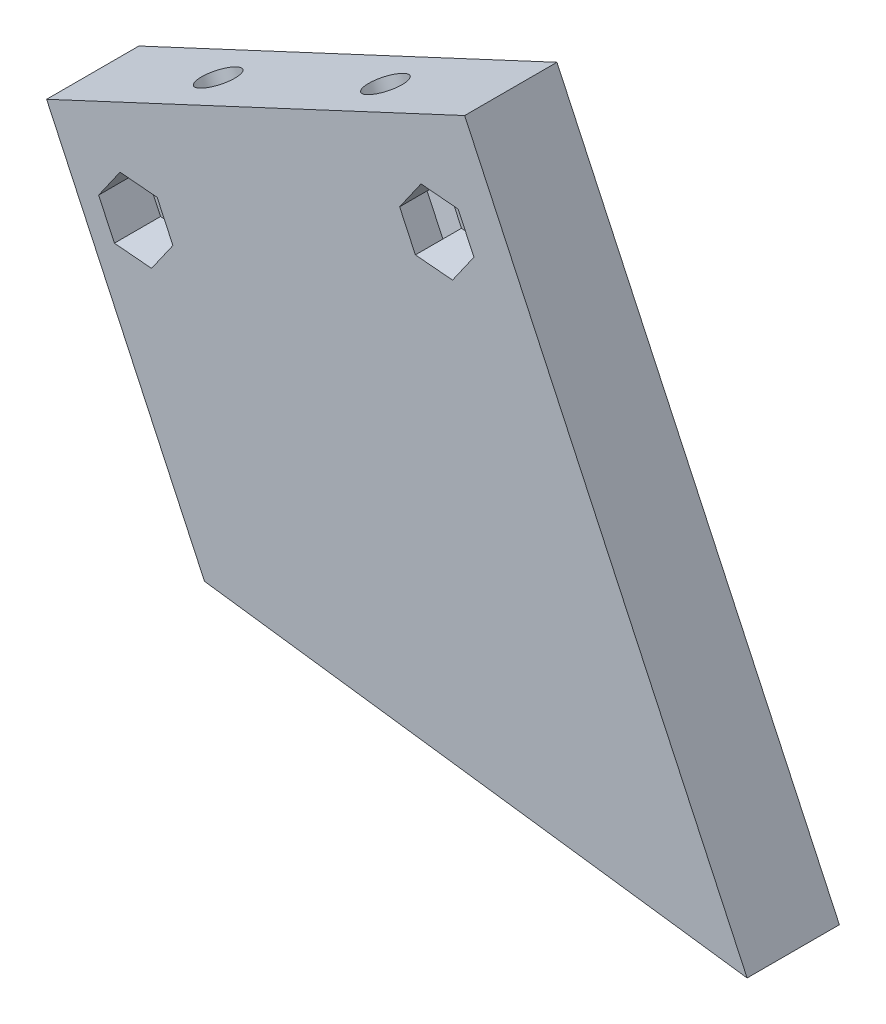
SolidWorks part; units mm, degrees
material "ABS"
ref_plane "Front Plane" through (0, 0, 0) normal (0, 0, 1) x (1, 0, 0)
ref_plane "Top Plane" through (0, 0, 0) normal (0, 1, 0) x (1, 0, 0)
ref_plane "Right Plane" through (0, 0, 0) normal (1, 0, 0) x (0, 0, -1)
sketch "Sketch1" plane through (0, 0, 0) normal (0, 0, 1) x (1, 0, 0)
  line L0 (117.7638, -15.9332) -> (87.1479, 49.7228)
  line L1 (273.6131, -36.6769) -> (75.3615, -10.2894) construction
  line L2 (87.1479, 49.7228) -> (41.8325, 28.5919)
  line L3 (41.8325, 28.5919) -> (58.9442, -8.1043)
  line L4 (58.9442, -8.1043) -> (117.7638, -15.9332)
  line L5 (117.7638, -15.9332) -> (87.1479, 49.7228) construction
  line L6 (189.2372, 97.3278) -> (-129.7831, -51.4338) construction
  dimension "D1" = 50
extrude "Boss-Extrude1" add sketch "Sketch1" against normal blind 10
sketch "Sketch2" plane through (-3.4798, 7.4624, 0) normal (-0.4226, 0.9063, 0) x (0.9063, 0.4226, 0)
  line L0 (49.9966, 5) -> (99.9966, 5) construction
  line L1 (49.9966, 10) -> (49.9966, 0) construction
  line L2 (99.9966, 10) -> (99.9966, 0) construction
  line L3 (74.9966, 10) -> (74.9966, 0) construction
  line L4 (84.9966, 0.9585) -> (88.4966, 2.9793)
  line L5 (88.4966, 2.9793) -> (88.4966, 7.0207)
  line L6 (88.4966, 7.0207) -> (84.9966, 9.0415)
  line L7 (84.9966, 9.0415) -> (81.4966, 7.0207)
  line L8 (81.4966, 7.0207) -> (81.4966, 2.9793)
  line L9 (81.4966, 2.9793) -> (84.9966, 0.9585)
  line L10 (99.9966, 10) -> (49.9966, 10) construction
  line L11 (99.9966, 0) -> (49.9966, 0) construction
  line L12 (68.4966, 2.9793) -> (64.9966, 0.9585)
  line L13 (64.9966, 0.9585) -> (61.4966, 2.9793)
  line L14 (68.4966, 7.0207) -> (68.4966, 2.9793)
  line L15 (64.9966, 9.0415) -> (68.4966, 7.0207)
  line L16 (61.4966, 7.0207) -> (64.9966, 9.0415)
  line L17 (61.4966, 2.9793) -> (61.4966, 7.0207)
  circle A0 centre (84.9966, 5) radius 3.5 construction
  circle A1 centre (84.9966, 5) radius 2
  circle A2 centre (64.9966, 5) radius 3.5 construction
  circle A3 centre (64.9966, 5) radius 2
  dimension "D3" = 4
  dimension "D1" = 15
  dimension "D2" = 7
extrude "Cut-Extrude1" cut sketch "Sketch2" against normal through all contours A3 | A1 region at (73.5533, 43.3835, -5) region at (55.4272, 34.9312, -5)
extrude "Cut-Extrude2" cut sketch "Sketch2<3>" against normal through all from offset 4 offset against normal yes
sketch "Sketch2<3>" plane through (-3.4798, 7.4624, 0) normal (-0.4226, 0.9063, 0) x (0.9063, 0.4226, 0) same geometry as "Sketch2"
sketch "Sketch3" plane through (-0.0338, -0.2542, 0) normal (-0.1319, -0.9913, 0) x (0.9913, -0.1319, 0)
  line L0 (118.8365, -5) -> (59.4982, -5) construction
  line L1 (118.8365, -10) -> (118.8365, 0) construction
  line L2 (59.4982, -10) -> (59.4982, 0) construction
  circle A0 centre (82.6447, -5) radius 2
  circle A1 centre (102.7291, -5) radius 2
  circle A2 centre (102.7291, -5) radius 1.5 construction
  circle A3 centre (82.6447, -5) radius 1.5 construction
  dimension "D1" = 4
  dimension "D2" = 4
extrude "Cut-Extrude3" cut sketch "Sketch3" against normal blind 10
sketch "Sketch4" plane through (0, 0, 0) normal (0, 0, 1) x (1, 0, 0)
  line L0 (117.7638, -15.9332) -> (87.1479, 49.7228) construction
  line L1 (88.1497, 36.9265) -> (86.4417, 40.5893)
  line L2 (86.4417, 40.5893) -> (82.4157, 40.9416)
  line L3 (82.4157, 40.9416) -> (80.0976, 37.631)
  line L4 (80.0976, 37.631) -> (81.8056, 33.9682)
  line L5 (81.8056, 33.9682) -> (85.8317, 33.616)
  line L6 (85.8317, 33.616) -> (88.1497, 36.9265)
  line L7 (87.1479, 49.7228) -> (41.8325, 28.5919) construction
  line L8 (55.5227, 21.7123) -> (53.8147, 25.3751)
  line L9 (53.8147, 25.3751) -> (49.7886, 25.7273)
  line L10 (49.7886, 25.7273) -> (47.4705, 22.4167)
  line L11 (47.4705, 22.4167) -> (49.1785, 18.7539)
  line L12 (49.1785, 18.7539) -> (53.2046, 18.4017)
  line L13 (53.2046, 18.4017) -> (55.5227, 21.7123)
  line L14 (87.1479, 49.7228) -> (41.8325, 28.5919) construction
  line L15 (41.8325, 28.5919) -> (58.9442, -8.1043) construction
  circle A0 centre (84.1237, 37.2788) radius 2
  circle A1 centre (84.1237, 37.2788) radius 3.5 construction
  circle A2 centre (51.4966, 22.0645) radius 2
  circle A3 centre (51.4966, 22.0645) radius 3.5 construction
  dimension "D4" = 4
  dimension "D7" = 4
  dimension "D1" = 8
  dimension "D2" = 10
  dimension "D3" = 7
  dimension "D5" = 0
  dimension "D6" = 7
  dimension "D8" = 10
  dimension "D9" = 6
extrude "Cut-Extrude4" cut sketch "Sketch4" against normal blind 10 contours A0 | A2 region at (84.1237, 37.2788, 0) region at (51.4966, 22.0645, 0)
extrude "Cut-Extrude5" cut sketch "Sketch4<3>" against normal blind 5 from surface starting at face at (86.1237, 37.2788, 0)
sketch "Sketch4<3>" plane through (0, 0, 0) normal (0, 0, 1) x (1, 0, 0) same geometry as "Sketch4"
